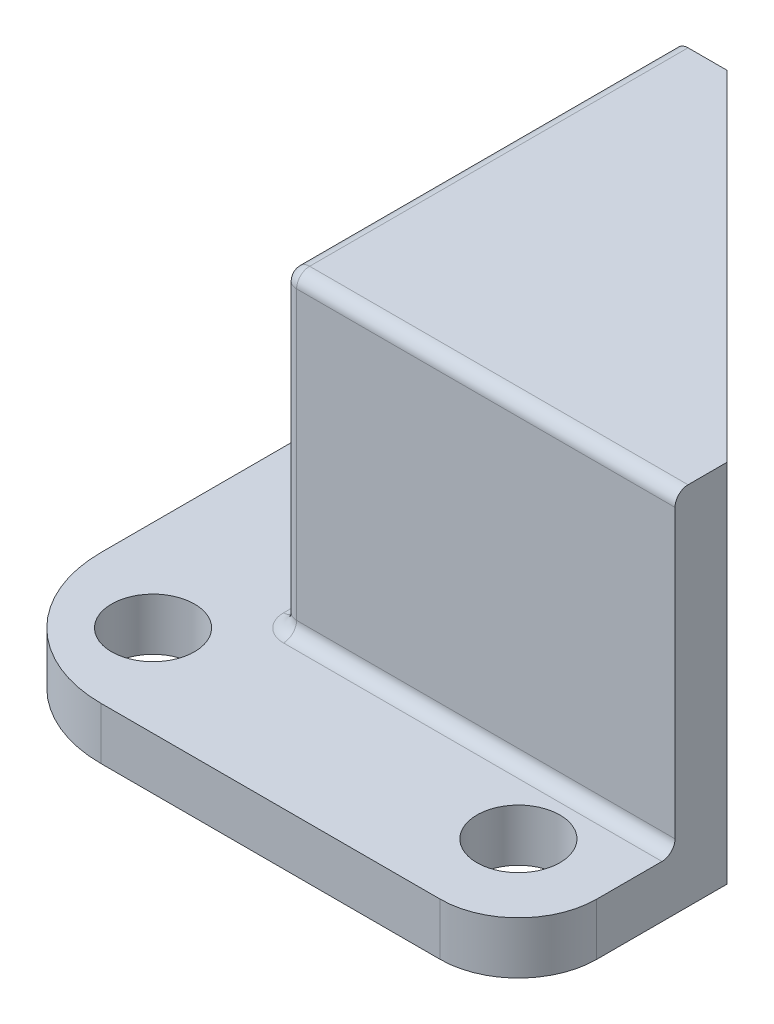
SolidWorks part; units mm, degrees
ref_plane "Front" through (0, 0, 0) normal (0, 0, 1) x (1, 0, 0)
ref_plane "Top" through (0, 0, 0) normal (0, 1, 0) x (1, 0, 0)
ref_plane "Right" through (0, 0, 0) normal (1, 0, 0) x (0, 0, -1)
sketch "Sketch1" plane through (0, 0, 0) normal (0, 1, 0) x (1, 0, 0)
  line L0 (0, 0) -> (0, 15)
  line L1 (0, 15) -> (2, 15)
  line L2 (2, 15) -> (2, 2)
  line L3 (2, 2) -> (15, 2)
  line L4 (15, 2) -> (15, 0)
  line L5 (15, 0) -> (0, 0)
  line L6 (0, 15) -> (-3, 15)
  line L7 (-6, 12) -> (-6, -1)
  line L8 (-1, -6) -> (12, -6)
  line L9 (15, -3) -> (15, 0)
  arc A0 (-1, -6) -> (-6, -1) centre (-1, -1) cw
  arc A1 (12, -6) -> (15, -3) centre (12, -3) ccw
  arc A2 (-3, 15) -> (-6, 12) centre (-3, 12) ccw
  point P14 (15, -6)
  point P17 (-6, 15)
  dimension "D8" = 5
  dimension "D9" = 3
  dimension "D10" = 3
  dimension "D1" = 15
  dimension "D2" = 15
  dimension "D3" = 13
  dimension "D4" = 13
  dimension "D5" = 2
  dimension "D6" = 6
  dimension "D7" = 6
extrude "Boss-Extrude1" add sketch "Sketch1" along normal blind 12 contours L5 L4 L3 L2 L1 L0 region at (0.2121, 0, -7.5)
extrude "Boss-Extrude2" add sketch "Sketch1<3>" along normal blind 2 contours L6 A2 L7 A0 L8 A1 L9 L5 L0 region at (7.5, 0, 0.297)
sketch "Sketch1<3>" plane through (0, 0, 0) normal (0, 1, 0) x (1, 0, 0) same geometry as "Sketch1"
ref_plane "Plane1" through (0, 12, 0) normal (0, 1, 0) x (1, 0, 0)
sketch "Sketch2" plane through (0, 12, 0) normal (0, 1, 0) x (1, 0, 0)
  line L0 (2, 15) -> (15, 2)
  line L1 (2, 15) -> (0, 15)
  line L2 (0, 15) -> (0, 0)
  line L3 (0, 0) -> (15, 0)
  line L4 (15, 0) -> (15, 2)
extrude "Boss-Extrude3" add sketch "Sketch2" along normal blind 2
sketch "Sketch3" plane through (0, 0, 0) normal (0, 1, 0) x (1, 0, 0)
  line L0 (0, 0) -> (15, 0) construction
  line L1 (0, 15) -> (0, 0) construction
  circle A0 centre (-2.5, -2.5) radius 1.5875
  circle A1 centre (-2.5, 11.5) radius 1.5875
  circle A2 centre (11.5, -2.5) radius 1.5875
  dimension "D1" = 3.175
  dimension "D2" = 3.175
  dimension "D3" = 3.175
  dimension "D4" = 2.5
  dimension "D5" = 2.5
  dimension "D6" = 14
  dimension "D7" = 14
extrude "Cut-Extrude1" cut sketch "Sketch3" against normal blind 2 and the other way blind 12
fillet "Fillet1" radius 0.5 5 edges at (0, 2, -7.5) (7.5, 2, 0) (7.5, 14, 0) (0, 8, 0) (0, 14, -7.5)
